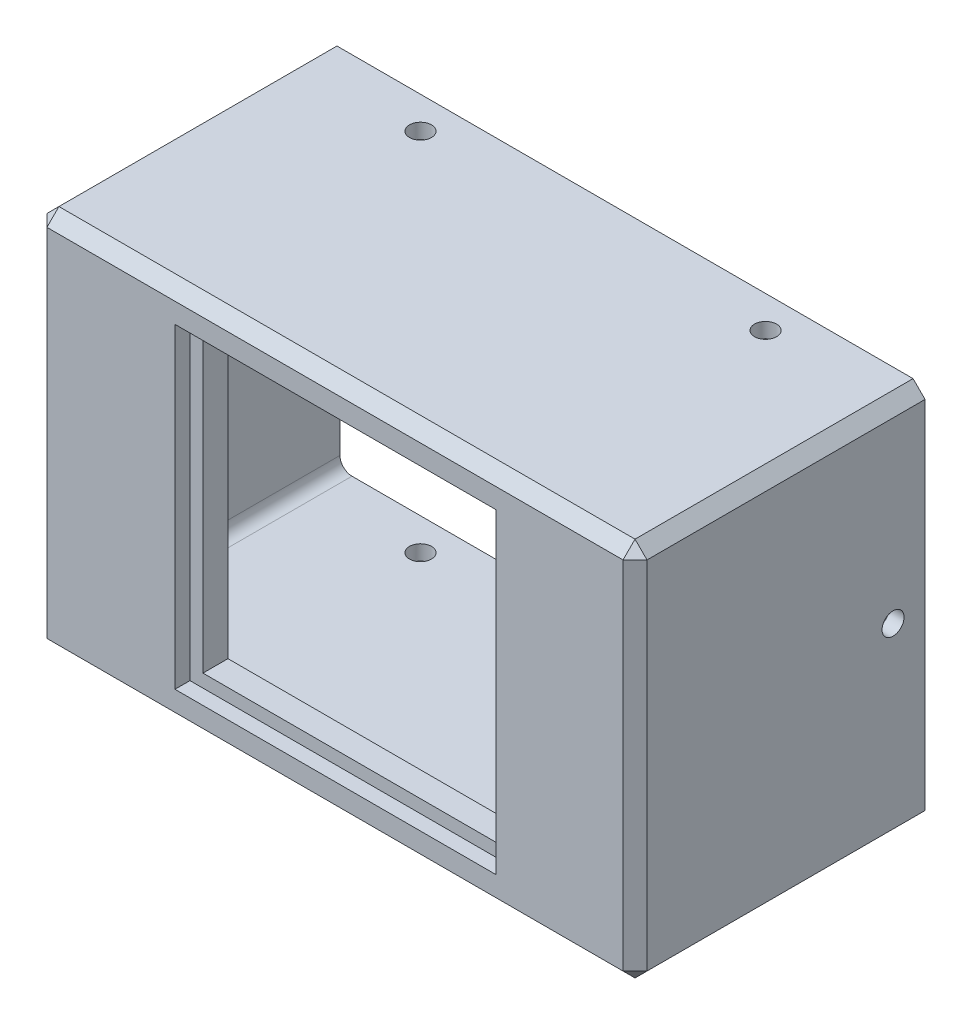
SolidWorks part; units mm, degrees
ref_plane "Plan de face" through (0, 0, 0) normal (0, 0, 1) x (1, 0, 0)
ref_plane "Plan de dessus" through (0, 0, 0) normal (0, 1, 0) x (1, 0, 0)
ref_plane "Plan de droite" through (0, 0, 0) normal (1, 0, 0) x (0, 0, -1)
sketch "Esquisse1" plane through (0, 0, 0) normal (0, 0, 1) x (1, 0, 0)
  line L1 (30, 19) -> (-30, 19)
  line L2 (30, 19) -> (30, -19)
  line L3 (30, -19) -> (-30, -19)
  line L4 (-30, 19) -> (-30, -19)
  line L5 (30, 19) -> (-30, -19) construction
  line L6 (30, -19) -> (-30, 19) construction
  point P0 (0, 0)
  point P6 (0, 0)
  dimension "D1" = 60
  dimension "D2" = 38
extrude "BASE" add sketch "Esquisse1" along normal blind 4
sketch "Esquisse2" plane through (0, 0, 4) normal (0, 0, 1) x (1, 0, 0)
  line L0 (-21.2, 0) -> (26.8, 0) construction
  line L1 (26.8, 16.5) -> (-21.2, 16.5) construction
  line L2 (26.8, 16.5) -> (26.8, -16.5) construction
  line L3 (26.8, -16.5) -> (-21.2, -16.5) construction
  line L4 (-21.2, 16.5) -> (-21.2, -16.5) construction
  line L5 (26.8, 16.5) -> (-21.2, -16.5) construction
  line L6 (26.8, -16.5) -> (-21.2, 16.5) construction
  line L7 (-14.7, 14.5) -> (14.8, 14.5)
  line L8 (-14.7, 14.5) -> (-14.7, -14.5)
  line L9 (-14.7, -14.5) -> (14.8, -14.5)
  line L10 (14.8, 14.5) -> (14.8, -14.5)
  line L11 (30, -19) -> (30, 19) construction
  point P0 (0, 0)
  dimension "D1" = 33
  dimension "D2" = 48
  dimension "D3" = 6.5
  dimension "D4" = 2
  dimension "D5" = 2
  dimension "D6" = 12
  dimension "D7" = 3.2
extrude "Screen" cut sketch "Esquisse2" against normal up to surface (4 mm away) up to face at (0, 0, 0)
sketch "Esquisse5" plane through (0, 0, 0) normal (0, 0, -1) x (-1, 0, 0)
  line L0 (2.2, 0) -> (-2.2, 0) construction
  line L1 (21.2, 16.5) -> (-26.8, 16.5) construction
  line L2 (21.2, 16.5) -> (21.2, -16.5) construction
  line L3 (21.2, -16.5) -> (-26.8, -16.5) construction
  line L4 (-26.8, 16.5) -> (-26.8, -16.5) construction
  line L5 (21.2, 16.5) -> (-26.8, -16.5) construction
  line L6 (21.2, -16.5) -> (-26.8, 16.5) construction
  line L8 (-2.8, 16.5) -> (-2.8, -16.5) construction
  circle A1 centre (-24.3, 14) radius 2.3
  circle A2 centre (-24.3, -14) radius 2.3
  circle A3 centre (18.7, -14) radius 2.3
  circle A4 centre (18.7, 14) radius 2.3
  point P0 (-0.8987, -1.3072)
  dimension "D3" = 4.6
  dimension "D1" = 48
  dimension "D2" = 33
  dimension "D4" = 2.5
  dimension "D5" = 2.5
extrude "Inserts_M3" cut sketch "Esquisse5" against normal blind 3
sketch "Esquisse6" plane through (0, 0, 0) normal (0, 0, -1) x (-1, 0, 0)
  line L0 (-28.5, 17.5) -> (-28.5, -17.5)
  line L1 (-30, 19) -> (30, 19)
  line L2 (-30, 19) -> (-30, -19)
  line L3 (-30, -19) -> (30, -19)
  line L4 (30, 19) -> (30, -19)
  line L5 (-28.5, -17.5) -> (28.5, -17.5)
  line L6 (28.5, 17.5) -> (28.5, -17.5)
  line L7 (-28.5, 17.5) -> (28.5, 17.5)
  dimension "D1" = 1.5
extrude "Walls" add sketch "Esquisse6" along normal blind 25
chamfer "Chanfrein_EXT" distance 1.2 angle 45 8 edges at (0, 19, 4) (30, 19, -10.5) (30, 0, 4) (30, -19, -10.5) (0, -19, 4) (-30, -19, -10.5) (-30, 0, 4) (-30, 19, -10.5)
fillet "Congé1" radius 1.2 8 edges at (0, 17.5, 0) (28.5, 0, 0) (-28.5, 0, 0) (0, -17.5, 0) (-28.5, -17.5, -12.5) (-28.5, 17.5, -12.5) (28.5, -17.5, -12.5) (28.5, 17.5, -12.5)
sketch "Esquisse7" plane through (30, 0, 0) normal (1, 0, 0) x (0, 0, -1)
  line L0 (25, 17.8) -> (25, -17.8) construction
  line L1 (-2.8, 17.8) -> (-2.8, -17.8) construction
  circle A0 centre (21.8, 0) radius 1.1
  point P7 (-2.8, 0)
  dimension "D1" = 2.2
  dimension "D2" = 3.2
extrude "Passage_Vis_Horizontal" cut sketch "Esquisse7" against normal through all
sketch "Esquisse9" plane through (0, 19, 0) normal (0, 1, 0) x (1, 0, 0)
  line L0 (-28.8, 25) -> (28.8, 25) construction
  line L2 (30, 25) -> (30, -2.8) construction
  line L4 (-30, -2.8) -> (-30, 25) construction
  circle A0 centre (-17.25, 21.8) radius 1.1
  circle A1 centre (17.25, 21.8) radius 1.1
  dimension "D1" = 2.2
  dimension "D2" = 3.2
  dimension "D3" = 12.75
  dimension "D4" = 12.75
extrude "Passage_Vis_Vertical" cut sketch "Esquisse9" against normal through all
sketch "Esquisse11" plane through (0, 0, 4) normal (0, 0, 1) x (1, 0, 0)
  line L1 (-16, 15.8) -> (16.1, 15.8)
  line L2 (-16, 15.8) -> (-16, -15.8)
  line L3 (-16, -15.8) -> (16.1, -15.8)
  line L4 (16.1, 15.8) -> (16.1, -15.8)
  line L6 (-14.7, 14.5) -> (-14.7, -14.5) construction
  line L7 (-14.7, -14.5) -> (14.8, -14.5) construction
  line L8 (14.8, 14.5) -> (-14.7, 14.5) construction
  line L13 (14.8, -14.5) -> (14.8, 14.5) construction
  dimension "D1" = 1.3
  dimension "D2" = 1.3
  dimension "D3" = 1.3
  dimension "D4" = 1.3
extrude "Emplacement Verre 32.5*32" cut sketch "Esquisse11" against normal blind 1.5 contours L2 L3 L4 L1
equation "\"D2@Esquisse11\"=\"D1@Esquisse11\""
equation "\"D3@Esquisse11\"=\"D1@Esquisse11\""
equation "\"D4@Esquisse11\"=\"D1@Esquisse11\""
